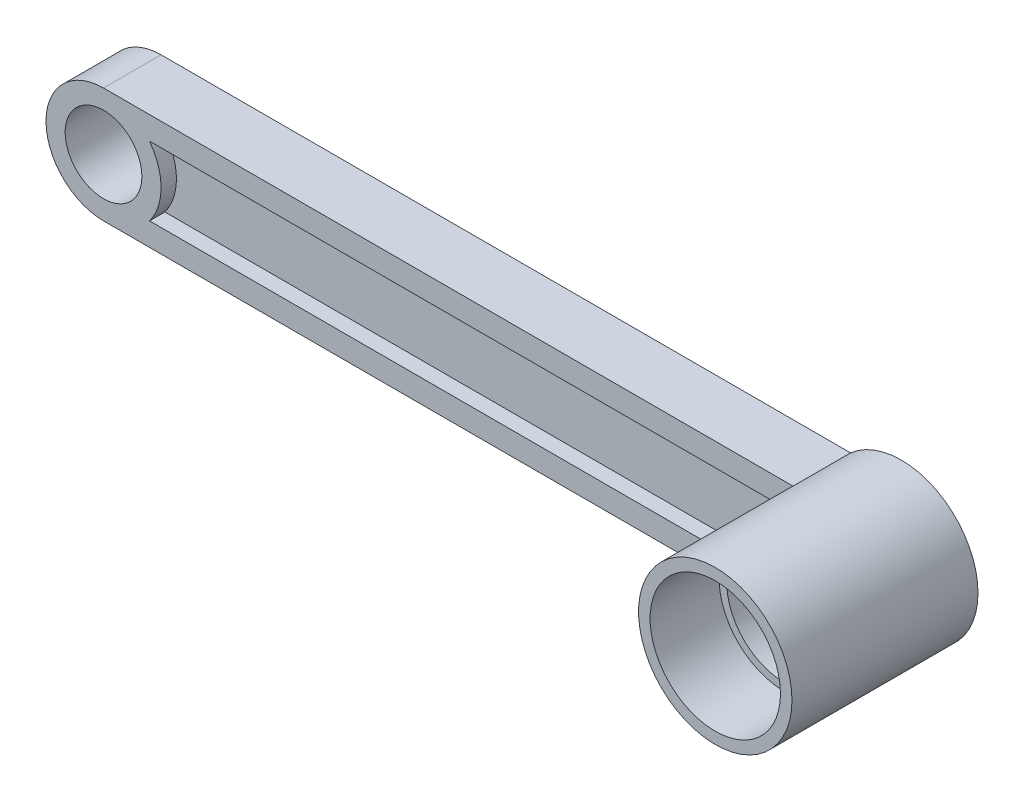
SolidWorks part; units mm, degrees
ref_plane "前视基准面" through (0, 0, 0) normal (0, 0, 1) x (1, 0, 0)
ref_plane "上视基准面" through (0, 0, 0) normal (0, 1, 0) x (1, 0, 0)
ref_plane "右视基准面" through (0, 0, 0) normal (1, 0, 0) x (0, 0, -1)
sketch "草图1" plane through (0, 0, 0) normal (1, 0, 0) x (0, 0, -1)
  line L11 (3.75, 0) -> (3.75, 7.5)
  line L12 (3.75, 7.5) -> (-3.75, 7.5)
  line L13 (-3.75, 7.5) -> (-3.75, -7.5)
  line L14 (-3.75, -7.5) -> (3.75, -7.5)
  line L15 (3.75, -7.5) -> (3.75, 0)
  dimension "D2" = 7.5
  dimension "D3" = 7.5
  dimension "D4" = 15
  dimension "D5" = 7.5
extrude "凸台-拉伸1" add sketch "草图1" along normal blind 48.25 and the other way blind 48.25
sketch "草图2" plane through (0, 0, 0) normal (0, 0, 1) x (1, 0, 0)
  line L0 (-48.25, 7.5) -> (-48.25, -7.5) construction
  circle A0 centre (-48.25, 0) radius 5
  circle A1 centre (-48.25, 0) radius 7.5
  dimension "D1" = 10
extrude "凸台-拉伸2" add sketch "草图2" along normal blind 3.75 and the other way blind 3.75
sketch "草图3" plane through (0, 0, 0) normal (0, 0, 1) x (1, 0, 0)
  line L0 (-48.25, 5) -> (-48.25, -5) construction
  circle A0 centre (-48.25, 0) radius 5
extrude "切除-拉伸1" cut sketch "草图3" against normal blind 3.75 and the other way blind 3.75
sketch "草图4" plane through (0, 0, 0) normal (0, 0, 1) x (1, 0, 0)
  circle A0 centre (48.25, 0) radius 10
  dimension "D1" = 20
extrude "凸台-拉伸3" add sketch "草图4" along normal blind 11.5 and the other way blind 3.75
sketch "草图8" plane through (0, 0, 3.75) normal (0, 0, 1) x (1, 0, 0)
  line L0 (-59.7112, 0) -> (60.2475, 0) construction
  line L1 (0, 0) -> (0, 4.5) construction
  line L2 (0, 4.5) -> (-42.25, 4.5)
  line L3 (0, 4.5) -> (39.3197, 4.5)
  line L4 (0, -4.5) -> (39.3197, -4.5)
  line L5 (0, -4.5) -> (-42.25, -4.5)
  arc A2 (-42.25, 4.5) -> (-42.25, -4.5) centre (-48.25, 0) cw
  arc A3 (39.3197, -4.5) -> (39.3197, 4.5) centre (48.25, 0) cw
  dimension "D1" = 4.5
extrude "切除-拉伸4" cut sketch "草图8" against normal blind 2
sketch "草图9" plane through (0, 0, 11.5) normal (0, 0, 1) x (1, 0, 0)
  circle A0 centre (48.25, 0) radius 7.5
  dimension "D1" = 15
extrude "切除-拉伸5" cut sketch "草图9" against normal blind 5
sketch "草图10" plane through (0, 0, 11.5) normal (0, 0, 1) x (1, 0, 0)
  circle A0 centre (48.25, 0) radius 8.5
  circle A1 centre (48.25, 0) radius 10
  dimension "D1" = 17
extrude "凸台-拉伸5" add sketch "草图10" along normal blind 9
sketch "草图11" plane through (0, 0, 6.5) normal (0, 0, 1) x (1, 0, 0)
  circle A0 centre (48.25, 0) radius 2.95
  dimension "D1" = 5.9
extrude "切除-拉伸6" cut sketch "草图11" against normal blind 2
sketch "草图12" plane through (0, 0, -3.75) normal (0, 0, -1) x (-1, 0, 0)
  circle A0 centre (-48.25, 0) radius 5.5
  dimension "D1" = 11
extrude "切除-拉伸7" cut sketch "草图12" against normal blind 6
sketch "草图13" plane through (0, 0, 2.25) normal (0, 0, -1) x (-1, 0, 0)
  circle A0 centre (-48.25, 0) radius 2.95
  dimension "D1" = 5.9
extrude "切除-拉伸8" cut sketch "草图13" against normal blind 6
